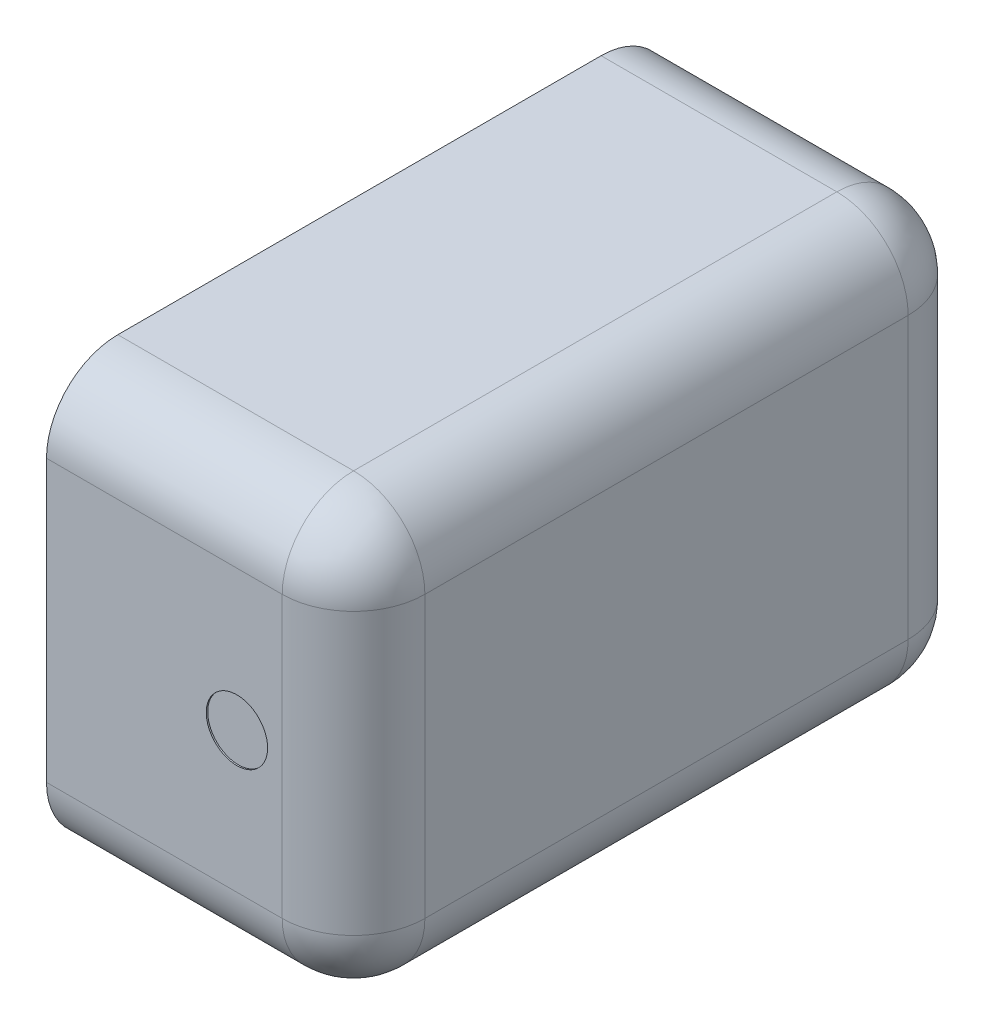
SolidWorks part; units mm, degrees
ref_plane "Front Plane" through (0, 0, 0) normal (0, 0, 1) x (1, 0, 0)
ref_plane "Top Plane" through (0, 0, 0) normal (0, 1, 0) x (1, 0, 0)
ref_plane "Right Plane" through (0, 0, 0) normal (1, 0, 0) x (0, 0, -1)
sketch "Sketch1" plane through (0, 0, 0) normal (1, 0, 0) x (0, 0, -1)
  line L1 (-43.875, 29.675) -> (43.875, 29.675)
  line L2 (-43.875, 29.675) -> (-43.875, -29.675)
  line L3 (-43.875, -29.675) -> (43.875, -29.675)
  line L4 (43.875, 29.675) -> (43.875, -29.675)
  line L5 (-43.875, 29.675) -> (43.875, -29.675) construction
  line L6 (-43.875, -29.675) -> (43.875, 29.675) construction
  point P0 (0, 0)
extrude "Boss-Extrude1" add sketch "Sketch1" along normal blind 43.05
sketch "Sketch2" plane through (0, 0, 43.875) normal (0, 0, 1) x (1, 0, 0)
  line L0 (43.05, 0) -> (31, 0) construction
  line L1 (43.05, 29.675) -> (43.05, -29.675) construction
  line L2 (31, 0) -> (26.7, 0) construction
  circle A0 centre (26.7, 0) radius 4.3
  dimension "D1" = 8.6
fillet "Fillet1" radius 10 8 edges at (21.525, 29.675, -43.875) (21.525, -29.675, -43.875) (43.05, -29.675, 0) (43.05, 0, -43.875) (43.05, 29.675, 0) (21.525, 29.675, 43.875) (43.05, 0, 43.875) (21.525, -29.675, 43.875)
ref_point "Point1"
extrude "Cut-Extrude1" cut sketch "Sketch2" against normal blind 0.2
ref_axis "Axis1" through (0, 0, 0) along (0, 0, 1)
